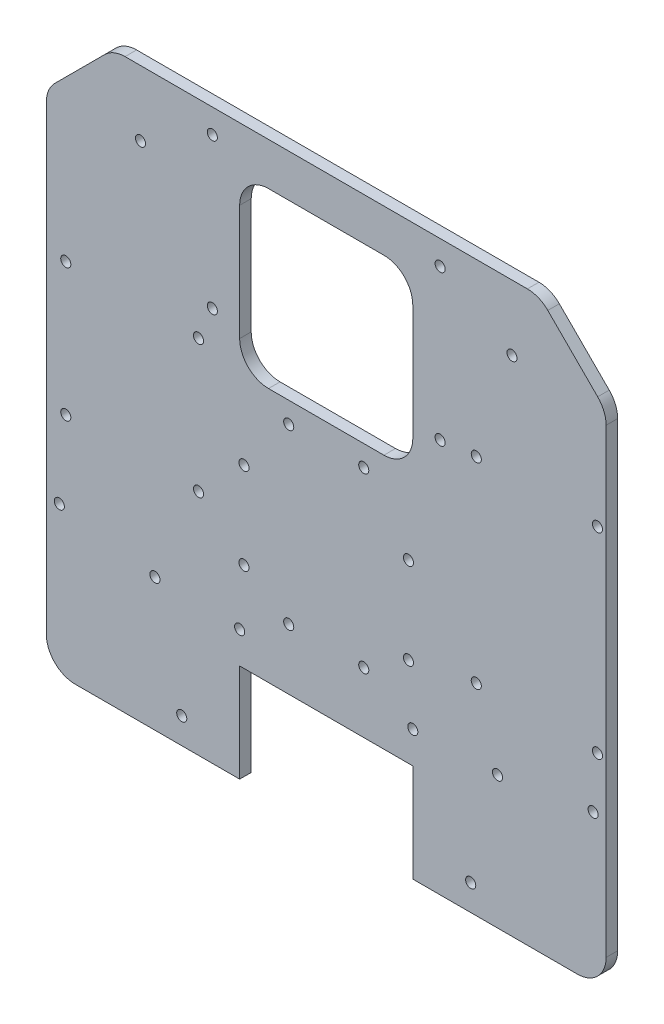
SolidWorks part; units mm, degrees
material "PMMA"
ref_plane "前视基准面" through (0, 0, 0) normal (0, 0, 1) x (1, 0, 0)
ref_plane "上视基准面" through (0, 0, 0) normal (0, 1, 0) x (1, 0, 0)
ref_plane "右视基准面" through (0, 0, 0) normal (1, 0, 0) x (0, 0, -1)
sketch "草图3" plane through (0, 0, 0) normal (0, 0, 1) x (1, 0, 0)
  line L1 (73.5057, 259.0895) -> (196.9372, 259.0895)
  line L2 (25.2215, 210.8052) -> (25.2215, 54.0895)
  line L3 (45.2215, 34.0895) -> (225.2215, 34.0895)
  line L4 (245.2215, 210.8052) -> (245.2215, 54.0895)
  line L6 (31.0793, 224.9474) -> (59.3636, 253.2316)
  line L9 (211.0793, 253.2316) -> (239.3636, 224.9474)
  arc A0 (73.5057, 259.0895) -> (59.3636, 253.2316) centre (73.5057, 239.0895) ccw
  arc A1 (211.0793, 253.2316) -> (196.9372, 259.0895) centre (196.9372, 239.0895) ccw
  arc A2 (31.0793, 224.9474) -> (25.2215, 210.8052) centre (45.2215, 210.8052) ccw
  arc A3 (25.2215, 54.0895) -> (45.2215, 34.0895) centre (45.2215, 54.0895) ccw
  arc A4 (225.2215, 34.0895) -> (245.2215, 54.0895) centre (225.2215, 54.0895) ccw
  arc A5 (245.2215, 210.8052) -> (239.3636, 224.9474) centre (225.2215, 210.8052) ccw
  dimension "D1" = 20
  dimension "D2" = 20
  dimension "D3" = 20
extrude "凸台-拉伸1" add sketch "草图3" along normal blind 4
ref_plane "基准面1" through (0, 0, 4) normal (0, 0, 1) x (1, 0, 0)
sketch "草图4" plane through (0, 0, 4) normal (0, 0, 1) x (1, 0, 0)
  line L0 (135.2215, 259.0895) -> (135.2215, 34.0895) construction
  line L1 (135.2215, 232.7454) -> (174.6915, 232.7454) construction
  line L2 (154.9565, 232.7454) -> (154.9565, 180.6354) construction
  line L4 (135.2215, 180.6354) -> (154.9565, 180.6354) construction
  line L6 (154.9565, 206.6904) -> (187.4334, 206.6904) construction
  line L10 (196.9372, 259.0895) -> (73.5057, 259.0895) construction
  line L11 (45.2215, 34.0895) -> (225.2215, 34.0895) construction
  line L13 (135.2215, 89.0683) -> (165.2215, 89.0683) construction
  circle A5 centre (174.6915, 232.7454) radius 1.75
  circle A14 centre (174.6915, 180.6354) radius 1.75
  circle A15 centre (95.7515, 180.6354) radius 1.75
  circle A16 centre (95.7515, 232.7454) radius 1.75
  circle A17 centre (165.2215, 89.0683) radius 1.75
  circle A18 centre (105.2215, 89.0683) radius 1.75
sketch "草图6" plane through (0, 0, 4) normal (0, 0, 1) x (1, 0, 0)
  line L0 (135.2215, 265.6507) -> (135.2215, 27.2875) construction
  line L1 (187.2215, 181.8801) -> (229.2215, 181.8801) construction
  line L3 (187.2215, 113.8801) -> (229.2215, 113.8801) construction
  line L5 (187.2215, 181.8801) -> (187.2215, 113.8801) construction
  circle A0 centre (187.2215, 181.8801) radius 1.75
  circle A1 centre (229.2215, 181.8801) radius 1.75
  circle A2 centre (229.2215, 113.8801) radius 1.75
  circle A3 centre (187.2215, 113.8801) radius 1.75
extrude "切除-拉伸3" cut sketch "草图6" against normal blind 4
extrude "切除-拉伸4" cut sketch "草图4" against normal blind 4
sketch "草图7" plane through (0, 0, 4) normal (0, 0, 1) x (1, 0, 0)
  circle A0 centre (122.2215, 159.0895) radius 1.75
  circle A1 centre (148.2215, 159.0895) radius 1.75
  circle A2 centre (122.2215, 99.0895) radius 1.75
  circle A3 centre (148.2215, 99.0895) radius 1.75
extrude "切除-拉伸5" cut sketch "草图7" against normal blind 4
sketch "草图8" plane through (0, 0, 4) normal (0, 0, 1) x (1, 0, 0)
  line L0 (25.2215, 132.4474) -> (245.2215, 132.4474) construction
  line L1 (105.2215, 89.0683) -> (165.2215, 89.0683) construction
  line L2 (227.7201, 95.4947) -> (185.2937, 53.0683) construction
  line L4 (25.2215, 210.8052) -> (25.2215, 54.0895) construction
  line L5 (245.2215, 210.8052) -> (245.2215, 54.0895) construction
  line L7 (135.2215, 259.0895) -> (135.2215, 34.0895) construction
  circle A2 centre (227.7201, 95.4947) radius 1.75
  circle A3 centre (185.2937, 53.0683) radius 1.75
  circle A4 centre (42.7229, 95.4947) radius 1.75
  circle A5 centre (85.1493, 53.0683) radius 1.75
extrude "切除-拉伸6" cut sketch "草图8" against normal blind 4
sketch "草图9" plane through (0, 0, 4) normal (0, 0, 1) x (1, 0, 0)
  line L0 (115.2215, 166.3247) -> (155.2215, 166.3247)
  line L2 (135.2215, 226.3247) -> (115.2215, 226.3247)
  line L6 (155.2215, 226.3247) -> (135.2215, 226.3247)
  line L9 (105.2215, 196.1043) -> (105.2215, 176.3247)
  line L10 (105.2215, 166.3247) -> (115.2215, 166.3247)
  line L11 (115.2215, 226.3247) -> (105.2215, 226.3247)
  line L12 (105.2215, 216.3247) -> (105.2215, 196.1043)
  line L13 (155.2215, 226.3247) -> (165.2215, 226.3247)
  line L14 (165.2215, 216.3247) -> (165.2215, 176.3247)
  line L15 (165.2215, 166.3247) -> (155.2215, 166.3247)
  arc A0 (165.2215, 216.3247) -> (155.2215, 226.3247) centre (155.2215, 216.3247) ccw
  arc A1 (165.2215, 176.3247) -> (155.2215, 166.3247) centre (155.2215, 176.3247) cw
  arc A2 (115.2215, 166.3247) -> (105.2215, 176.3247) centre (115.2215, 176.3247) cw
  arc A3 (105.2215, 216.3247) -> (115.2215, 226.3247) centre (115.2215, 216.3247) cw
  dimension "D1" = 10
extrude "切除-拉伸7" cut sketch "草图9" against normal blind 4 contours L0 L6 L2 L11 region at (135.2215, 196.3247, 4)
sketch "草图10" plane through (0, 0, 4) normal (0, 0, 1) x (1, 0, 0)
  line L0 (135.2215, 259.0895) -> (135.2215, 34.0895) construction
  line L1 (196.9372, 259.0895) -> (73.5057, 259.0895) construction
  line L2 (45.2215, 34.0895) -> (225.2215, 34.0895) construction
  line L3 (106.7215, 109.0895) -> (106.7215, 139.0895) construction
  line L4 (106.7215, 139.0895) -> (163.7215, 139.0895) construction
  line L5 (163.7215, 139.0895) -> (163.7215, 109.0895) construction
  line L6 (163.7215, 109.0895) -> (106.7215, 109.0895) construction
  line L7 (45.2215, 34.0895) -> (225.2215, 34.0895) construction
  circle A2 centre (106.7215, 109.0895) radius 1.75
  circle A3 centre (163.7215, 109.0895) radius 1.75
  circle A4 centre (106.7215, 139.0895) radius 1.75
  circle A5 centre (163.7215, 139.0895) radius 1.75
  dimension "D1" = 75
extrude "切除-拉伸9" cut sketch "草图10" against normal blind 4
sketch "草图11" plane through (0, 0, 4) normal (0, 0, 1) x (1, 0, 0)
  line L0 (26.7439, 218.4589) -> (243.6991, 218.4589) construction
  line L1 (65.8521, 257.5671) -> (65.8521, 34.0895) construction
  line L2 (45.2215, 34.0895) -> (225.2215, 34.0895) construction
  line L3 (204.5909, 131.2717) -> (65.8521, 131.2717) construction
  line L4 (25.2215, 54.0895) -> (245.2215, 54.0895) construction
  line L5 (135.2215, 259.0895) -> (135.2215, 34.0895) construction
  line L10 (73.254, 90.0846) -> (74.553, 87.8346)
  line L11 (73.4502, 218.4589) -> (72.1511, 220.7089)
  line L12 (196.9372, 259.0895) -> (73.5057, 259.0895) construction
  line L13 (204.5909, 218.4589) -> (204.5909, 44.0846) construction
  line L26 (75.8521, 90.0846) -> (75.8521, 218.4589) construction
  line L27 (72.1511, 220.7089) -> (69.553, 220.7089)
  line L28 (69.553, 220.7089) -> (68.254, 218.4589)
  line L29 (68.254, 218.4589) -> (69.553, 216.2089)
  line L30 (69.553, 216.2089) -> (72.1511, 216.2089)
  line L31 (72.1511, 216.2089) -> (73.4502, 218.4589)
  line L32 (77.1511, 87.8346) -> (78.4502, 90.0846)
  line L33 (74.553, 87.8346) -> (77.1511, 87.8346)
  line L34 (78.4502, 90.0846) -> (77.1511, 92.3346)
  line L35 (74.553, 92.3346) -> (73.254, 90.0846)
  line L36 (77.1511, 92.3346) -> (74.553, 92.3346)
  line L37 (191.9928, 90.0846) -> (193.2918, 87.8346)
  line L38 (195.8899, 87.8346) -> (197.1889, 90.0846)
  line L39 (193.2918, 87.8346) -> (195.8899, 87.8346)
  line L40 (197.1889, 90.0846) -> (195.8899, 92.3346)
  line L41 (193.2918, 92.3346) -> (191.9928, 90.0846)
  line L42 (195.8899, 92.3346) -> (193.2918, 92.3346)
  line L43 (196.9928, 218.4589) -> (198.2918, 216.2089)
  line L44 (200.8899, 216.2089) -> (202.1889, 218.4589)
  line L45 (198.2918, 216.2089) -> (200.8899, 216.2089)
  line L46 (202.1889, 218.4589) -> (200.8899, 220.7089)
  line L47 (198.2918, 220.7089) -> (196.9928, 218.4589)
  line L48 (200.8899, 220.7089) -> (198.2918, 220.7089)
  arc A0 (31.0793, 224.9474) -> (25.2215, 210.8052) centre (45.2215, 210.8052) ccw construction
  arc A1 (245.2215, 210.8052) -> (239.3636, 224.9474) centre (225.2215, 210.8052) ccw construction
  arc A2 (73.5057, 259.0895) -> (59.3636, 253.2316) centre (73.5057, 239.0895) ccw construction
  circle A3 centre (70.8521, 218.4589) radius 1.75
  circle A12 centre (75.8521, 90.0846) radius 1.75
  circle A13 centre (194.5909, 90.0846) radius 1.75
  circle A15 centre (199.5909, 218.4589) radius 1.75
  circle A16 centre (70.8521, 218.4589) radius 2.25 construction
  point P26 (65.8521, 218.4589)
  dimension "D1" = 4.5
extrude "切除-拉伸10" cut sketch "草图11" against normal up to next contours L29 | A3 | A12 | A13 | A15 region at (70.8521, 218.4589, 4) region at (75.8521, 90.0846, 4) region at (194.5909, 90.0846, 4) region at (199.5909, 218.4589, 4)
ref_plane "基准面2" through (0, 0, 4) normal (0, 0, 1) x (1, 0, 0)
sketch "草图12" plane through (0, 0, 4) normal (0, 0, 1) x (1, 0, 0)
  line L0 (41.9614, 172.3122) -> (41.9614, 165.6511) construction
  line L1 (41.9614, 172.3122) -> (93.9614, 172.3122)
  line L2 (41.9614, 172.3122) -> (41.9614, 120.3122)
  line L3 (41.9614, 120.3122) -> (93.9614, 120.3122)
  line L4 (93.9614, 172.3122) -> (93.9614, 120.3122)
  line L5 (41.9614, 172.3122) -> (93.9614, 120.3122) construction
  line L6 (41.9614, 120.3122) -> (93.9614, 172.3122) construction
  line L7 (41.9614, 172.3122) -> (41.9614, 166.5784) construction
  line L8 (41.9614, 166.5784) -> (41.9614, 164.5784) construction
  line L9 (93.9614, 172.3122) -> (93.9614, 169.3122) construction
  line L10 (93.9614, 169.3122) -> (90.9614, 169.3122) construction
  circle A0 centre (90.9614, 169.3122) radius 1.75
  circle A1 centre (90.9614, 123.3122) radius 1.75
  circle A2 centre (44.9614, 123.3122) radius 1.75
  circle A3 centre (44.9614, 169.3122) radius 1.75
  point P0 (67.9614, 146.3122)
  point P20 (67.9614, 146.3122)
  dimension "D1" = 4
extrude "切除-拉伸13" cut sketch "草图12" against normal through all contours A3 | A2 | A1 | A0
sketch "草图13" plane through (0, 0, 4) normal (0, 0, 1) x (1, 0, 0)
  line L0 (45.2215, 34.0895) -> (225.2215, 34.0895) construction
  line L1 (105.2215, 68.0683) -> (165.2215, 68.0683)
  line L2 (105.2215, 68.0683) -> (105.2215, 34.0895)
  line L3 (105.2215, 34.0895) -> (165.2215, 34.0895)
  line L4 (165.2215, 68.0683) -> (165.2215, 34.0895)
  line L5 (165.2215, 54.0895) -> (105.2215, 54.0895)
  line L6 (25.2215, 54.0895) -> (245.2215, 54.0895) construction
extrude "切除-拉伸14" cut sketch "草图13" against normal blind 10 contours L4 L5 L2 L3 | L2 L1 L4 L3 region at (135.2215, 44.0895, 4)
sketch "草图14" plane through (0, 0, 0) normal (0, 0, 1) x (1, 0, 0)
  line L0 (105.2215, 68.0683) -> (165.2215, 68.0683)
  line L10 (105.2215, 68.0683) -> (165.2215, 68.0683)
  line L11 (165.2215, 68.0683) -> (165.2215, 34.0895)
  line L12 (165.2215, 34.0895) -> (225.2215, 34.0895)
  line L13 (245.2215, 54.0895) -> (245.2215, 210.8052)
  line L14 (239.3636, 224.9474) -> (211.0793, 253.2316)
  line L15 (196.9372, 259.0895) -> (73.5057, 259.0895)
  line L16 (59.3636, 253.2316) -> (31.0793, 224.9474)
  line L17 (25.2215, 210.8052) -> (25.2215, 54.0895)
  line L18 (45.2215, 34.0895) -> (105.2215, 34.0895)
  line L19 (105.2215, 34.0895) -> (105.2215, 68.0683)
  line L21 (165.2215, 44.0895) -> (165.2215, 34.0895)
  line L22 (165.2215, 34.0895) -> (225.2215, 34.0895)
  line L23 (245.2215, 54.0895) -> (245.2215, 210.8052)
  line L24 (239.3636, 224.9474) -> (211.0793, 253.2316)
  line L25 (196.9372, 259.0895) -> (73.5057, 259.0895)
  line L26 (59.3636, 253.2316) -> (31.0793, 224.9474)
  line L27 (25.2215, 210.8052) -> (25.2215, 54.0895)
  line L28 (45.2215, 34.0895) -> (105.2215, 34.0895)
  line L29 (105.2215, 34.0895) -> (105.2215, 44.0895)
  line L30 (38.2215, 210.8052) -> (38.2215, 54.0895)
  line L31 (232.2215, 54.0895) -> (232.2215, 213.8052)
  line L32 (196.9372, 241.0895) -> (73.5057, 241.0895)
  line L33 (73.5057, 241.0895) -> (65.5057, 241.0895)
  line L34 (38.2215, 210.8052) -> (38.2215, 213.8052)
  line L35 (196.9372, 241.0895) -> (204.9372, 241.0895)
  line L36 (232.2215, 210.8052) -> (232.2215, 213.8052)
  line L40 (95.2215, 78.0683) -> (175.2215, 78.0683)
  line L41 (175.2215, 78.0683) -> (175.2215, 44.0895)
  line L42 (175.2215, 44.0895) -> (225.2215, 44.0895)
  line L43 (235.2215, 54.0895) -> (235.2215, 210.8052)
  line L44 (232.2925, 217.8763) -> (204.0083, 246.1606)
  line L45 (196.9372, 249.0895) -> (73.5057, 249.0895)
  line L46 (66.4347, 246.1606) -> (38.1504, 217.8763)
  line L47 (35.2215, 210.8052) -> (35.2215, 54.0895)
  line L48 (45.2215, 44.0895) -> (95.2215, 44.0895)
  line L49 (95.2215, 44.0895) -> (95.2215, 78.0683)
  line L50 (105.2215, 78.0683) -> (165.2215, 78.0683)
  line L52 (175.2215, 44.0895) -> (222.2215, 44.0895)
  line L54 (229.2925, 220.8763) -> (212.0083, 238.1606)
  line L56 (58.4347, 238.1606) -> (41.1504, 220.8763)
  line L58 (48.2215, 44.0895) -> (95.2215, 44.0895)
  line L61 (105.2215, 78.0683) -> (105.2215, 68.0683)
  line L62 (95.2215, 44.0895) -> (105.2215, 44.0895)
  line L63 (165.2215, 78.0683) -> (165.2215, 68.0683)
  line L64 (175.2215, 44.0895) -> (165.2215, 44.0895)
  arc A6 (225.2215, 34.0895) -> (245.2215, 54.0895) centre (225.2215, 54.0895) ccw
  arc A7 (245.2215, 210.8052) -> (239.3636, 224.9474) centre (225.2215, 210.8052) ccw
  arc A8 (211.0793, 253.2316) -> (196.9372, 259.0895) centre (196.9372, 239.0895) ccw
  arc A9 (73.5057, 259.0895) -> (59.3636, 253.2316) centre (73.5057, 239.0895) ccw
  arc A10 (31.0793, 224.9474) -> (25.2215, 210.8052) centre (45.2215, 210.8052) ccw
  arc A11 (25.2215, 54.0895) -> (45.2215, 34.0895) centre (45.2215, 54.0895) ccw
  arc A12 (225.2215, 34.0895) -> (245.2215, 54.0895) centre (225.2215, 54.0895) ccw
  arc A13 (245.2215, 210.8052) -> (239.3636, 224.9474) centre (225.2215, 210.8052) ccw
  arc A14 (211.0793, 253.2316) -> (196.9372, 259.0895) centre (196.9372, 239.0895) ccw
  arc A15 (73.5057, 259.0895) -> (59.3636, 253.2316) centre (73.5057, 239.0895) ccw
  arc A16 (31.0793, 224.9474) -> (25.2215, 210.8052) centre (45.2215, 210.8052) ccw
  arc A17 (25.2215, 54.0895) -> (45.2215, 34.0895) centre (45.2215, 54.0895) ccw
  arc A18 (222.2215, 44.0895) -> (232.2215, 54.0895) centre (222.2215, 54.0895) ccw
  arc A19 (48.2215, 44.0895) -> (38.2215, 54.0895) centre (48.2215, 54.0895) cw
  arc A20 (212.0083, 238.1606) -> (204.9372, 241.0895) centre (204.9372, 231.0895) ccw
  arc A21 (58.4347, 238.1606) -> (65.5057, 241.0895) centre (65.5057, 231.0895) cw
  arc A22 (232.2215, 213.8052) -> (229.2925, 220.8763) centre (222.2215, 213.8052) ccw
  arc A23 (38.2215, 213.8052) -> (41.1504, 220.8763) centre (48.2215, 213.8052) cw
  arc A24 (225.2215, 44.0895) -> (235.2215, 54.0895) centre (225.2215, 54.0895) ccw
  arc A25 (235.2215, 210.8052) -> (232.2925, 217.8763) centre (225.2215, 210.8052) ccw
  arc A26 (204.0083, 246.1606) -> (196.9372, 249.0895) centre (196.9372, 239.0895) ccw
  arc A27 (73.5057, 249.0895) -> (66.4347, 246.1606) centre (73.5057, 239.0895) ccw
  arc A28 (38.1504, 217.8763) -> (35.2215, 210.8052) centre (45.2215, 210.8052) ccw
  arc A29 (35.2215, 54.0895) -> (45.2215, 44.0895) centre (45.2215, 54.0895) ccw
  dimension "D3" = 10
  dimension "D4" = 10
  dimension "D1" = 0
  dimension "D2" = 10
extrude "切除-拉伸16" cut sketch "草图14" along normal blind 10 contours L34 A23 L56 A21 L33 L32 L35 A20 L54 A22 L31 A18 L52 L64 L21 L22 A12 L23 A13 L24 A14 L25 A15 L26 A16 L27 A17 L28 L29 L62 L58 A19 L30 | L63 L50 L61 L0 region at (135.2215, 73.0683, 0) region at (102.0747, 39.0895, 0) region at (36.8628, 130.2831, 0) region at (233.5801, 130.2831, 0) region at (135.2215, 244.9823, 0)
